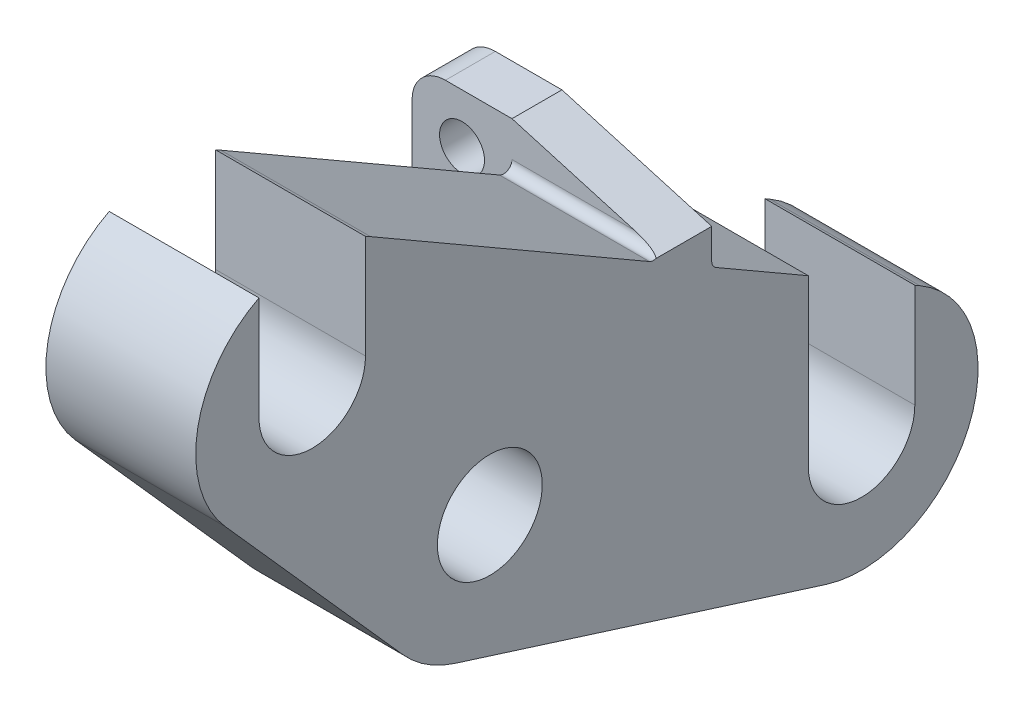
SolidWorks part; units mm, degrees
ref_plane "Front Plane" through (0, 0, 0) normal (0, 0, 1) x (1, 0, 0)
ref_plane "Top Plane" through (0, 0, 0) normal (0, 1, 0) x (1, 0, 0)
ref_plane "Right Plane" through (0, 0, 0) normal (1, 0, 0) x (0, 0, -1)
ref_plane "Plane4" through (9, 0, 0) normal (1, 0, 0) x (0, 0, -1)
sketch "Sketch1" plane through (9, 0, 0) normal (1, 0, 0) x (0, 0, -1)
  line L0 (3.5235, 220.1706) -> (3.2238, 220.3437)
  line L1 (-32.977, 233.1595) -> (-32.9759, 206.2902) construction
  line L2 (-29.777, 233.1595) -> (-29.777, 239.3852)
  line L3 (-38.2081, 228.508) -> (-27.5376, 216.508)
  line L4 (-24.4143, 214.4844) -> (-2.084, 207.4332)
  line L5 (-36.177, 233.1595) -> (-36.177, 239.3852)
  line L6 (3.2238, 214.1083) -> (3.2238, 220.3437)
  line L7 (-3.1762, 214.1083) -> (-3.1762, 224.0384)
  line L8 (-3.1762, 224.0384) -> (-29.4773, 239.2218)
  arc A0 (-36.177, 239.3852) -> (-38.2081, 228.508) centre (-32.977, 233.1595) ccw
  arc A1 (3.2238, 214.1083) -> (-3.1762, 214.1083) centre (0.0238, 214.1083) cw
  arc A2 (-29.777, 233.1595) -> (-36.177, 233.1595) centre (-32.977, 233.1595) cw
  arc A3 (-2.084, 207.4332) -> (3.5235, 220.1706) centre (0.0238, 214.1083) ccw
  arc A4 (-29.4773, 239.2218) -> (-29.777, 239.3852) centre (-32.977, 233.1595) ccw
  circle A6 centre (-22.3065, 221.1595) radius 3.15
  arc A7 (-27.5376, 216.508) -> (-24.4143, 214.4844) centre (-22.3065, 221.1595) ccw
  dimension "D1" = 6.3
  dimension "D2" = 6.4
  dimension "D3" = 7
  dimension "D4" = 38.1051
  dimension "D5" = 60
  dimension "D6" = 10.67
  dimension "D7" = 12
extrude "Boss-Extrude1" add sketch "Sketch1" against normal blind 9
sketch "Sketch2" plane through (0, 0, 0) normal (-1, 0, 0) x (0, 0, 1)
  line L0 (24.4143, 214.4844) -> (2.084, 207.4332) construction
  line L1 (8.9762, 232.1083) -> (11.9762, 232.1083)
  line L2 (8.9762, 232.1083) -> (8.9762, 209.6095)
  line L3 (8.9762, 209.6095) -> (11.9762, 210.5568)
  line L4 (11.9762, 232.1083) -> (11.9762, 210.5568)
  circle A0 centre (-0.0238, 214.1083) radius 3.2 construction
  dimension "D1" = 12
  dimension "D3" = 18
  dimension "D2" = 3
extrude "Boss-Extrude2" add sketch "Sketch2" along normal blind 6 and the other way up to surface (9 mm away) other way up to face at (9, 221.1595, 25.4565)
ref_axis "Axis1" through (0, 214.1083, -0.0238) along (1, 0, 0)
sketch "Sketch3" plane through (0, 0, 8.9762) normal (0, 0, -1) x (-1, 0, 0)
  line L0 (0, 207.1083) -> (0, 220.1706) construction
  line L2 (0, 214.1083) -> (-9, 214.1083) construction
  circle A0 centre (3, 229.1083) radius 1.35
  dimension "D2" = 2.7
  dimension "D1" = 3
  dimension "D3" = 15
extrude "Cut-Extrude1" cut sketch "Sketch3" against normal through all
chamfer "Chamfer1" distance 6 distance2 10 1 edges at (-6, 210.0832, 10.4762) first distance on face at (0.75, 210.521, 11.8627)
chamfer "Chamfer2" distance 2.6 distance2 9 1 edges at (9, 232.1083, 10.4762) first distance on face at (9, 221.1595, 25.4565)
fillet "Fillet1" radius 2 1 edges at (-6, 232.1083, 10.4762)
fillet "Fillet2" radius 0.5 1 edges at (4.5, 227.3867, 8.9762)
fillet "Fillet3" radius 0.5 1 edges at (4.5, 229.1186, 11.9762)
fillet "Fillet4" radius 1 1 edges at (0, 218.6424, 8.9762)
